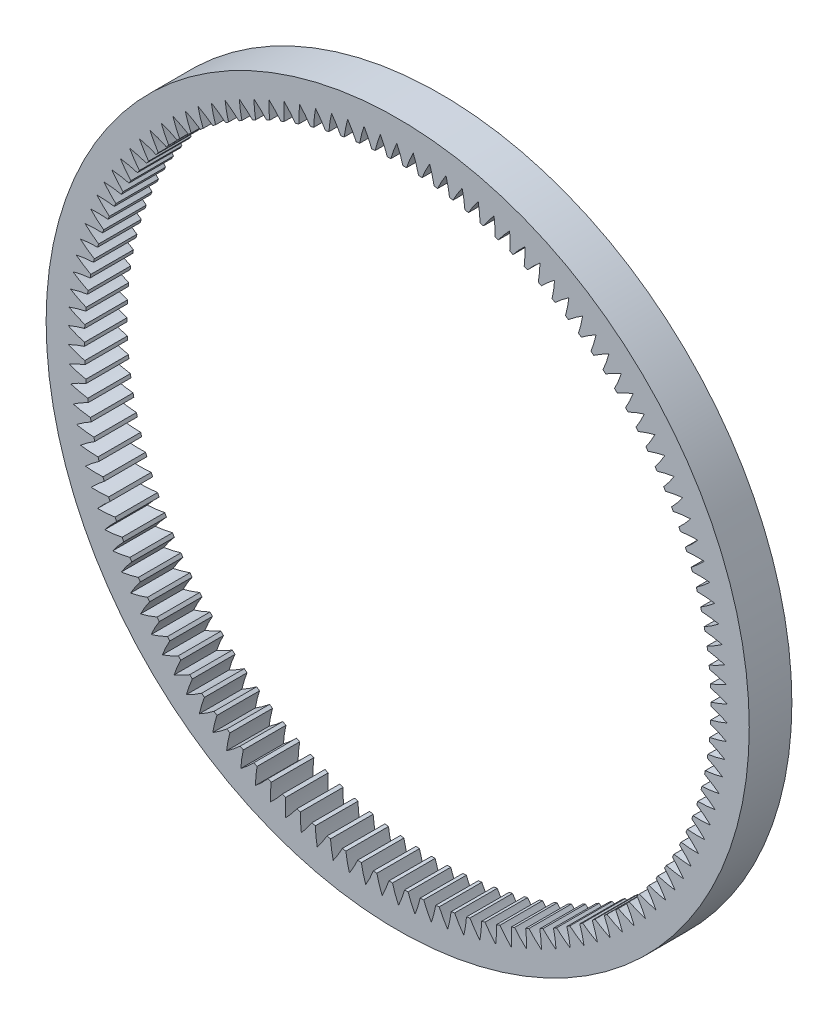
SolidWorks part; units mm, degrees
ref_plane "Front Plane" through (0, 0, 0) normal (0, 0, 1) x (1, 0, 0)
ref_plane "Top Plane" through (0, 0, 0) normal (0, 1, 0) x (1, 0, 0)
ref_plane "Right Plane" through (0, 0, 0) normal (1, 0, 0) x (0, 0, -1)
sketch "Sketch1" plane through (0, 0, 0) normal (0, 0, 1) x (1, 0, 0)
  line L0 (0, 0) -> (152.3804, 0.3964) construction
  line L1 (0, 0) -> (7.4762, 0.2059) construction
  line L2 (0, 0) -> (152.3804, 0.3964) construction
  line L3 (0, 0) -> (152.3637, 2.296) construction
  line L4 (0, 0) -> (152.1713, 7.9915) construction
  line L5 (147.0233, 0.3825) -> (164.9994, 0.4293)
  line L6 (7.4762, 0.2059) -> (164.9375, 4.5427)
  circle A0 centre (0, 0) radius 150 construction
  circle A1 centre (0, 0) radius 147.0238 construction
  circle A2 centre (0, 0) radius 140.9539 construction
  circle A3 centre (0, 0) radius 152.381 construction
  arc A4 (146.9949, 2.9152) -> (147.0233, 0.3825) centre (0, 0) cw
  arc A5 (164.9375, 4.5427) -> (164.9994, 0.4293) centre (0, 0) cw
  spline S0 degree 4 poles (140.9539, 0) (141.047, 0.0021) (141.233, 0.0096) (141.6043, 0.0381) (142.1413, 0.0988) (142.7502, 0.1881) (143.5952, 0.3382) (144.7155, 0.5763) (146.1211, 0.9353) (148.5424, 1.6703) (151.8418, 2.9113) (156.3125, 4.9787) (161.7974, 8.1307) (167.5079, 12.0923) (173.2947, 16.8502) (178.7179, 22.0165) (183.7842, 27.5321) (188.7334, 33.6368) (194.3854, 41.5588) (200.3945, 51.493) (206.3549, 63.5923) (211.0515, 75.8366) (214.322, 86.5835) (217.006, 97.4872) (218.7638, 106.6813) (220.0572, 115.9516) (220.9004, 125.2707) (221.3104, 132.7451) (221.4993, 142.1002) (221.2188, 153.3279) (220.176, 166.3924) (218.4445, 178.4384) (216.692, 187.63) (215.3753, 193.5675) (214.7345, 196.2984) (214.1768, 198.5735) (213.7205, 200.3797) (213.2864, 202.0439) (212.8968, 203.5028) (212.5227, 204.8688) (212.2249, 205.9419) (211.8226, 207.3585) (211.531, 208.3682) (211.0466, 210.0184) (210.6618, 211.2901) (210.1884, 212.8378) (209.7547, 214.2166) (209.2845, 215.691) (208.8222, 217.1072) (208.224, 218.9088) (207.4957, 221.0461) (206.6187, 223.5443) (205.7164, 226.0241) (204.9217, 228.1477) (204.3824, 229.5564) (204.1096, 230.2614) (203.9728, 230.6129) knots 0 0 0 0 0 0.001401 0.002802 0.005604 0.008133 0.010661 0.015718 0.022839 0.02996 0.048734 0.068727 0.096889 0.125051 0.153212 0.181374 0.209535 0.237696 0.271429 0.327752 0.384075 0.440398 0.46856 0.496721 0.553044 0.581206 0.609367 0.637529 0.66569 0.722013 0.778336 0.834659 0.84874 0.86282 0.869861 0.876901 0.883942 0.890982 0.895509 0.900036 0.904564 0.909091 0.914773 0.920455 0.926136 0.931818 0.9375 0.943182 0.948864 0.954545 0.965909 0.977273 0.988636 0.994318 1 1 1 1 1 construction
  spline S1 degree 4 poles (140.9539, 0) (141.047, 0.0021) (141.233, 0.0096) (141.6043, 0.0381) (142.1413, 0.0988) (142.7502, 0.1881) (143.5952, 0.3382) (144.7155, 0.5763) (146.1211, 0.9353) (148.5424, 1.6703) (151.8418, 2.9113) (156.3125, 4.9787) (161.7974, 8.1307) (167.5079, 12.0923) (173.2947, 16.8502) (178.7179, 22.0165) (183.7842, 27.5321) (188.7334, 33.6368) (194.3854, 41.5588) (200.3945, 51.493) (206.3549, 63.5923) (211.0515, 75.8366) (214.322, 86.5835) (217.006, 97.4872) (218.7638, 106.6813) (220.0572, 115.9516) (220.9004, 125.2707) (221.3104, 132.7451) (221.4993, 142.1002) (221.2188, 153.3279) (220.176, 166.3924) (218.4445, 178.4384) (216.692, 187.63) (215.3753, 193.5675) (214.7345, 196.2984) (214.1768, 198.5735) (213.7205, 200.3797) (213.2864, 202.0439) (212.8968, 203.5028) (212.5227, 204.8688) (212.2249, 205.9419) (211.9413, 206.9407) (211.7889, 207.4725) (211.7131, 207.7353) knots 0 0 0 0 0 0.001401 0.002802 0.005604 0.008133 0.010661 0.015718 0.022839 0.02996 0.048734 0.068727 0.096889 0.125051 0.153212 0.181374 0.209535 0.237696 0.271429 0.327752 0.384075 0.440398 0.46856 0.496721 0.553044 0.581206 0.609367 0.637529 0.66569 0.722013 0.778336 0.834659 0.84874 0.86282 0.869861 0.876901 0.883942 0.890982 0.895509 0.900036 0.904564 0.909091 0.909091 0.909091 0.909091 0.909091
  point P6 (147.0071, 2.2153)
  point P14 (147.0188, 1.2154)
  point P19 (146.9949, 2.9152)
  dimension "pitchRadius" = 150
  dimension "addendumRadius" = 152.381
  dimension "dedendumRadius" = 147.0238
  dimension "baseRadius" = 140.9539
  dimension "D1" = 1.429
  dimension "D2" = 0.714
  dimension "toothArc" = 2.857
  dimension "backlash" = 1
  dimension "D3" = 165
extrude "Boss-Extrude1" add sketch "Sketch1" along normal blind 20 contours S1 region at (157.4775, 2.1954, 0)
mirror "Mirror1" about plane through (0, 0, 20) normal (-0.0275, 0.9996, 0) of "Boss-Extrude1"
pattern_circular "CirPattern2" count 126 over 360 about axis through (0, 0, 20) along (0, 0, -1) of "Boss-Extrude1", "Mirror1"
ref_axis "Axis1" through (0, 0, 0) along (0, 0, 1)
equation "\"D2@Sketch1\"=\"toothArc@Sketch1\"/4"
equation "\"pitchRadius\"= 15"
equation "\"nTeeth\"= 126"
equation "\"pressureAngle\"= 20"
equation "\"baseRadius\"= \"pitchRadius\" * cos ( \"pressureAngle\" )"
equation "\"diametralPitch\"= \"nTeeth\" / ( 2 * \"pitchRadius\" )'note units: cm^-1"
equation "\"dedendum\"= 1.25 / \"diametralPitch\"'for full depth, 20 deg pressure angle"
equation "\"addendum\"= 1 / \"diametralPitch\""
equation "\"pitchRadius@Sketch1\"= \"pitchRadius\""
equation "\"addendumRadius@Sketch1\"= \"pitchRadius\" + \"addendum\""
equation "\"dedendumRadius@Sketch1\"= \"pitchRadius\" - \"dedendum\""
equation "\"baseRadius@Sketch1\"= \"baseRadius\""
equation "\"D2@CirPattern2\"= \"nTeeth\""
equation "\"D1@CirPattern2\"=\"nTeeth\""
equation "\"toothArc@Sketch1\"=360/\"nTeeth\""
equation "\"D1@Sketch1\"=\"toothArc@Sketch1\"/2"
